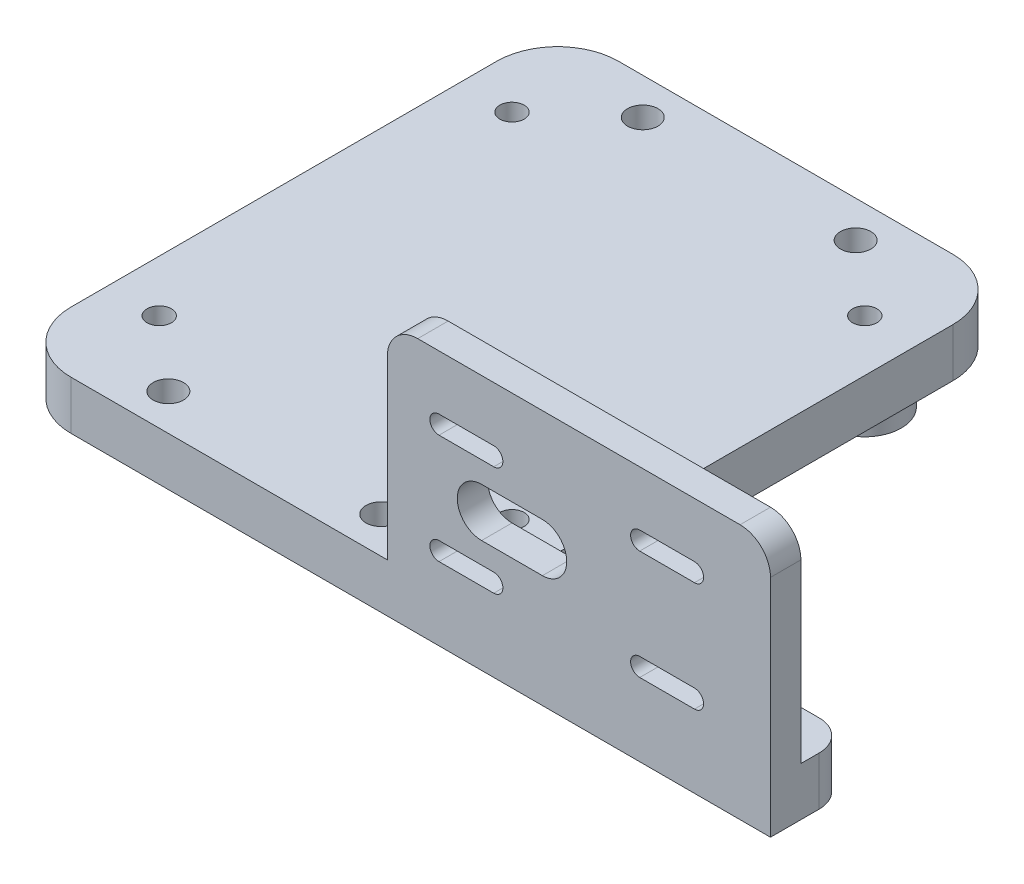
SolidWorks part; units mm, degrees
ref_plane "Front Plane" through (0, 0, 0) normal (0, 0, 1) x (1, 0, 0)
ref_plane "Top Plane" through (0, 0, 0) normal (0, 1, 0) x (1, 0, 0)
ref_plane "Right Plane" through (0, 0, 0) normal (1, 0, 0) x (0, 0, -1)
sketch "Sketch1" plane through (0, 0, 0) normal (0, 1, 0) x (1, 0, 0)
  line L1 (0, 0) -> (75, 0)
  line L2 (0, 0) -> (0, -90)
  line L3 (0, -90) -> (75, -90)
  line L4 (75, 0) -> (75, -90)
  line L5 (75, -90) -> (125, -90)
  line L6 (75, -90) -> (75, -77)
  line L7 (75, -77) -> (125, -77)
  line L8 (125, -90) -> (125, -77)
  dimension "D1" = 90
  dimension "D2" = 75
  dimension "D3" = 50
  dimension "D4" = 13
extrude "Boss-Extrude1" add sketch "Sketch1" along normal blind 8 contours L4 L1 L2 L3 | L5 L8 L7 L4 region at (37.5, 0, 45) region at (100, 0, 83.5)
sketch "Sketch2" plane through (0, 0, 0) normal (0, -1, 0) x (1, 0, 0)
  line L0 (37.5, 0) -> (37.5, 90) construction
  line L1 (0, 0) -> (75, 0) construction
  line L2 (0, 90) -> (125, 90) construction
  circle A0 centre (37.5, 45) radius 15.5
  circle A1 centre (37.5, 45) radius 18
extrude "Boss-Extrude2" add sketch "Sketch2" along normal blind 5 contours A1 | A0
sketch "Sketch3" plane through (0, 0, 0) normal (0, -1, 0) x (1, 0, 0)
  line L0 (37.5, 45) -> (53, 45) construction
  line L2 (8.5, 16) -> (66.5, 16)
  line L3 (8.5, 16) -> (8.5, 74)
  line L4 (8.5, 74) -> (66.5, 74)
  line L5 (66.5, 16) -> (66.5, 74)
  line L6 (8.5, 16) -> (66.5, 74) construction
  line L7 (8.5, 74) -> (66.5, 16) construction
  circle A0 centre (37.5, 45) radius 15.5 construction
  circle A1 centre (8.5, 74) radius 2
  circle A2 centre (66.5, 74) radius 2
  circle A3 centre (8.5, 16) radius 2
  circle A4 centre (66.5, 16) radius 2
  dimension "D1" = 58
  dimension "D2" = 58
extrude "Cut-Extrude2" cut sketch "Sketch3" against normal through all both and the other way through all contours A1 | A2 | A3 | A4
fillet "Fillet2" radius 10 1 edges at (0, 4, 0) type face fillet first side face at (37.5, 4, 0) second side face at (0, 4, 45)
fillet "Fillet3" radius 10 1 edges at (0, 4, 90) type face fillet first side face at (62.5, 4, 90) second side face at (0, 4, 50)
fillet "Fillet4" radius 10 1 edges at (75, 4, 0) type face fillet first side face at (42.5, 4, 0) second side face at (75, 4, 38.5)
sketch "Sketch5" plane through (0, 0, 0) normal (0, -1, 0) x (1, 0, 0)
  line L0 (37.5, 45) -> (37.5, 90) construction
  line L1 (10, 90) -> (125, 90) construction
  line L2 (37.5, 45) -> (75, 45)
  line L3 (37.5, 90) -> (55, 90)
  line L4 (37.5, 90) -> (37.5, 84)
  line L5 (37.5, 84) -> (55, 84)
  line L6 (55, 90) -> (55, 84)
  line L7 (75, 10) -> (75, 77) construction
  circle A0 centre (55, 84) radius 2.5
  circle A1 centre (20, 84) radius 2.5
  circle A2 centre (55, 6) radius 2.5
  circle A3 centre (20, 6) radius 2.5
  dimension "D1" = 17.5
  dimension "D2" = 6
extrude "Cut-Extrude3" cut sketch "Sketch5" against normal up to next contours A2 | A1 | A0 | A3 region at (55, 0, 6)
sketch "Sketch7" plane through (125, 0, 0) normal (1, 0, 0) x (0, 0, -1)
  line L1 (-90, 8) -> (-85, 8)
  line L2 (-90, 8) -> (-90, 42)
  line L3 (-90, 42) -> (-85, 42)
  line L4 (-85, 8) -> (-85, 42)
  dimension "D1" = 34
  dimension "D2" = 5
extrude "Boss-Extrude3" add sketch "Sketch7" against normal blind 63
fillet "Fillet5" radius 5 1 edges at (125, 42, 87.5) type face fillet first side face at (125, 16.6667, 84) second side face at (93.5, 42, 87.5)
fillet "Fillet6" radius 5 1 edges at (125, 4, 77) type face fillet first side face at (125, 15, 84) second side face at (100, 4, 77)
fillet "Fillet7" radius 5 1 edges at (62, 42, 87.5) type face fillet first side face at (91, 42, 87.5) second side face at (62, 25, 87.5)
sketch "Sketch11" plane through (0, 8, 0) normal (0, 1, 0) x (1, 0, 0)
  line L0 (20, -84) -> (55, -84) construction
  line L1 (37.5, -84) -> (37.5, -90) construction
  line L2 (10, -90) -> (62, -90) construction
sketch "Sketch12" plane through (0, 0, 90) normal (0, 0, 1) x (1, 0, 0)
  line L0 (37.5, 8) -> (77.5, 8)
  line L1 (20, 8) -> (55, 8) construction
  line L2 (62, 22.5) -> (125, 22.5) construction
  line L3 (62, 37) -> (62, 8) construction
  line L4 (125, 37) -> (125, 0) construction
  line L5 (77.5, 22.5) -> (87.5, 22.5) construction
  line L6 (77.5, 8) -> (87.5, 8)
  line L7 (77.5, 8) -> (77.5, 22.5)
  line L8 (77.5, 22.5) -> (87.5, 22.5)
  line L9 (87.5, 8) -> (87.5, 22.5)
  line L10 (77.5, 26.5) -> (87.5, 26.5)
  line L11 (77.5, 18.5) -> (87.5, 18.5)
  line L12 (70.5, 31.5) -> (79.5, 31.5) construction
  line L13 (77.5, 22.5) -> (70.5, 22.5)
  line L14 (77.5, 22.5) -> (77.5, 31.5)
  line L15 (77.5, 31.5) -> (70.5, 31.5)
  line L16 (70.5, 22.5) -> (70.5, 31.5)
  line L17 (70.5, 33) -> (79.5, 33)
  line L18 (70.5, 30) -> (79.5, 30)
  line L19 (70.5, 13.5) -> (79.5, 13.5) construction
  line L20 (70.5, 12) -> (79.5, 12)
  line L21 (70.5, 15) -> (79.5, 15)
  line L22 (103.5, 31.5) -> (112.5, 31.5) construction
  line L23 (103.5, 33) -> (112.5, 33)
  line L24 (103.5, 30) -> (112.5, 30)
  line L25 (103.5, 13.5) -> (112.5, 13.5) construction
  line L26 (103.5, 12) -> (112.5, 12)
  line L27 (103.5, 15) -> (112.5, 15)
  arc A0 (77.5, 26.5) -> (77.5, 18.5) centre (77.5, 22.5) ccw
  arc A1 (87.5, 18.5) -> (87.5, 26.5) centre (87.5, 22.5) ccw
  arc A2 (70.5, 33) -> (70.5, 30) centre (70.5, 31.5) ccw
  arc A3 (79.5, 30) -> (79.5, 33) centre (79.5, 31.5) ccw
  arc A4 (70.5, 12) -> (70.5, 15) centre (70.5, 13.5) cw
  arc A5 (79.5, 15) -> (79.5, 12) centre (79.5, 13.5) cw
  arc A6 (103.5, 33) -> (103.5, 30) centre (103.5, 31.5) ccw
  arc A7 (112.5, 30) -> (112.5, 33) centre (112.5, 31.5) ccw
  arc A8 (103.5, 12) -> (103.5, 15) centre (103.5, 13.5) cw
  arc A9 (112.5, 15) -> (112.5, 12) centre (112.5, 13.5) cw
  point P13 (82.5, 22.5)
  point P22 (75, 31.5)
  point P30 (75, 13.5)
  point P38 (108, 31.5)
  point P46 (108, 13.5)
  dimension "D2" = 7
  dimension "D4" = 2
  dimension "D1" = 10
  dimension "D3" = 9
extrude "Cut-Extrude4" cut sketch "Sketch12" against normal up to next contours L18 A3 L17 A2 | L24 A7 L23 A6 | L27 A9 L26 A8 | L21 A5 L20 A4 | L11 A1 L10 A0
sketch "Sketch13" plane through (0, 0, 0) normal (0, -1, 0) x (1, 0, 0)
  circle A0 centre (8.5, 74) radius 6
  circle A1 centre (66.5, 74) radius 6
  circle A2 centre (66.5, 16) radius 6
  circle A3 centre (8.5, 16) radius 6
  circle A4 centre (8.5, 74) radius 2
  circle A5 centre (66.5, 74) radius 2
  circle A6 centre (66.5, 16) radius 2
  circle A7 centre (8.5, 16) radius 2
  dimension "D1" = 2
  dimension "D2" = 2
  dimension "D3" = 2
  dimension "D4" = 2
extrude "Boss-Extrude4" add sketch "Sketch13" along normal blind 5
